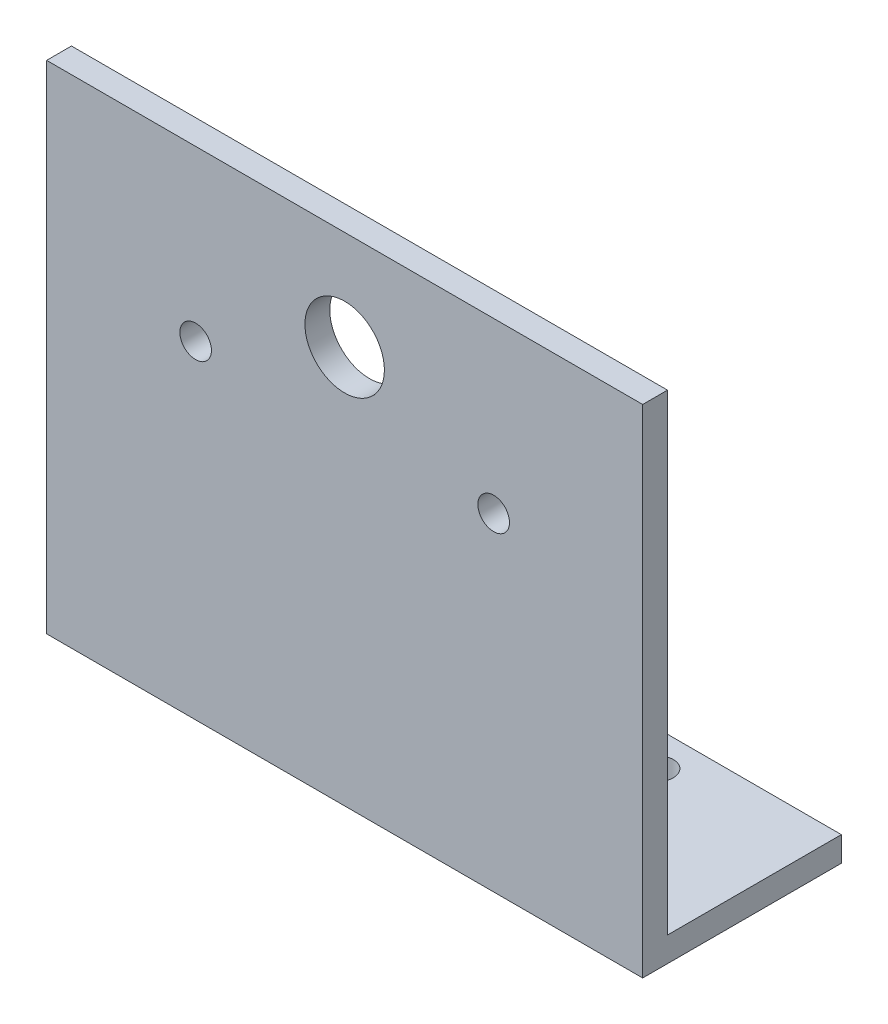
SolidWorks part; units mm, degrees
ref_plane "Front Plane" through (0, 0, 0) normal (0, 0, 1) x (1, 0, 0)
ref_plane "Top Plane" through (0, 0, 0) normal (0, 1, 0) x (1, 0, 0)
ref_plane "Right Plane" through (0, 0, 0) normal (1, 0, 0) x (0, 0, -1)
sketch "Sketch1" plane through (0, 0, 0) normal (0, 0, 1) x (1, 0, 0)
  line L1 (38.1, 21.59) -> (-38.1, 21.59)
  line L2 (38.1, 21.59) -> (38.1, -41.91)
  line L3 (38.1, -41.91) -> (-38.1, -41.91)
  line L4 (-38.1, 21.59) -> (-38.1, -41.91)
  line L5 (0, 0) -> (0, 8.89) construction
  circle A0 centre (0, 8.89) radius 5.08
  point P0 (0, 0)
extrude "Boss-Extrude1" add sketch "Sketch1" along normal blind 3.175
hole_wizard "#10-32 Tapped Hole1" positions "Sketch5" profile "Sketch4" tap size "#10-32" standard "Ansi Inch"
sketch "Sketch5" plane through (0, 0, 3.175) normal (0, 0, 1) x (1, 0, 0)
  line L0 (0, 0) -> (-19.05, 0)
  line L2 (0, 0) -> (19.05, 0)
  point P0 (-19.05, 0)
sketch "Sketch4" plane through (-19.05, 0, 3.175) normal (1, 0, 0) x (0, -1, 0)
  line L0 (0, 0) -> (0, 13.1513)
  line L1 (0, 13.1513) -> (2.0193, 11.938)
  line L2 (2.0193, 11.938) -> (2.0193, 0)
  line L5 (2.0193, 0) -> (0, 0)
  line L10 (0, 13.1513) -> (-2.0193, 11.938) construction
  line L11 (0, -6.35) -> (0, 107.95) construction
  dimension "Tap Drill Dia." = 4.0386
  dimension "Tap Drill Depth" = 11.938
  dimension "Drill Angle" = 118
cosmetic thread "Hole Thread1" parameters "D1"=3.175, "D2"=4.826
hole_wizard "#10-32 Tapped Hole2" positions "Sketch7" profile "Sketch6" tap size "#10-32" standard "Ansi Inch"
sketch "Sketch7" plane through (0, 0, 3.175) normal (0, 0, 1) x (1, 0, 0)
  point P0 (19.05, 0)
sketch "Sketch6" plane through (19.05, 0, 3.175) normal (1, 0, 0) x (0, -1, 0)
  line L0 (0, 0) -> (0, 13.1513)
  line L1 (0, 13.1513) -> (2.0193, 11.938)
  line L2 (2.0193, 11.938) -> (2.0193, 0)
  line L5 (2.0193, 0) -> (0, 0)
  line L10 (0, 13.1513) -> (-2.0193, 11.938) construction
  line L11 (0, -6.35) -> (0, 107.95) construction
  dimension "Tap Drill Dia." = 4.0386
  dimension "Tap Drill Depth" = 11.938
  dimension "Drill Angle" = 118
cosmetic thread "Hole Thread2" parameters "D1"=3.175, "D2"=4.826
sketch "Sketch10" plane through (0, 0, 0) normal (0, 0, -1) x (-1, 0, 0)
  line L0 (38.1, 21.59) -> (38.1, -41.91) construction
  line L1 (-38.1, -41.91) -> (38.1, -41.91)
  line L2 (-38.1, -41.91) -> (-38.1, -38.735)
  line L3 (-38.1, -38.735) -> (38.1, -38.735)
  line L4 (38.1, -41.91) -> (38.1, -38.735)
extrude "Boss-Extrude2" add sketch "Sketch10" along normal blind 22.225
hole_wizard "#10-32 Tapped Hole3" positions "Sketch12" profile "Sketch11" tap size "#10-32" standard "Ansi Inch"
sketch "Sketch12" plane through (0, -38.735, 0) normal (0, 1, 0) x (-1, 0, 0)
  point P0 (19.05, -17.78)
sketch "Sketch11" plane through (-19.05, -38.735, -17.78) normal (1, 0, 0) x (0, 0, 1)
  line L0 (0, 0) -> (0, 13.1513)
  line L1 (0, 13.1513) -> (2.0193, 11.938)
  line L2 (2.0193, 11.938) -> (2.0193, 0)
  line L5 (2.0193, 0) -> (0, 0)
  line L10 (0, 13.1513) -> (-2.0193, 11.938) construction
  line L11 (0, -6.35) -> (0, 107.95) construction
  dimension "Tap Drill Dia." = 4.0386
  dimension "Tap Drill Depth" = 11.938
  dimension "Drill Angle" = 118
cosmetic thread "Hole Thread3" parameters "D1"=3.175, "D2"=4.826
hole_wizard "#10-32 Tapped Hole4" positions "Sketch14" profile "Sketch13" tap size "#10-32" standard "Ansi Inch"
sketch "Sketch14" plane through (0, -38.735, 0) normal (0, 1, 0) x (-1, 0, 0)
  point P0 (-19.05, -17.78)
sketch "Sketch13" plane through (19.05, -38.735, -17.78) normal (1, 0, 0) x (0, 0, 1)
  line L0 (0, 0) -> (0, 13.1513)
  line L1 (0, 13.1513) -> (2.0193, 11.938)
  line L2 (2.0193, 11.938) -> (2.0193, 0)
  line L5 (2.0193, 0) -> (0, 0)
  line L10 (0, 13.1513) -> (-2.0193, 11.938) construction
  line L11 (0, -6.35) -> (0, 107.95) construction
  dimension "Tap Drill Dia." = 4.0386
  dimension "Tap Drill Depth" = 11.938
  dimension "Drill Angle" = 118
cosmetic thread "Hole Thread4" parameters "D1"=3.175, "D2"=4.826
